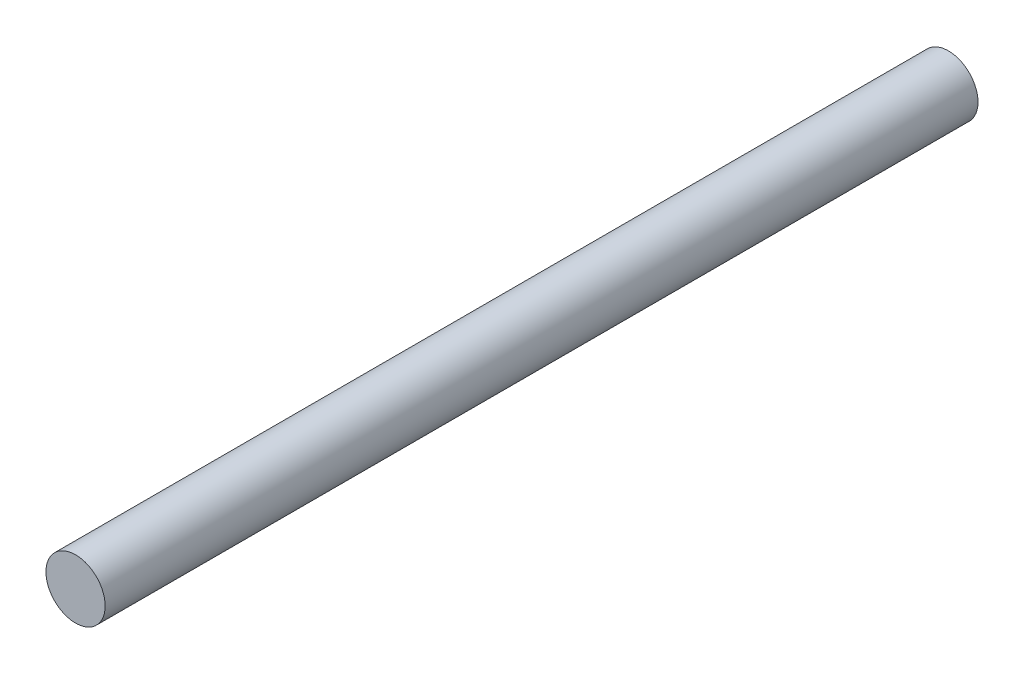
SolidWorks part; units mm, degrees
material "Thornel Mat VMA"
ref_plane "Front Plane" through (0, 0, 0) normal (0, 0, 1) x (1, 0, 0)
ref_plane "Top Plane" through (0, 0, 0) normal (0, 1, 0) x (1, 0, 0)
ref_plane "Right Plane" through (0, 0, 0) normal (1, 0, 0) x (0, 0, -1)
sketch "Sketch1" plane through (0, 0, 0) normal (0, 0, 1) x (1, 0, 0)
  circle A0 centre (0, 0) radius 9
  dimension "D1" = 18
extrude "Boss-Extrude1" add sketch "Sketch1" along normal blind 265.32
equation "\"fuse_diam\"= 0.07"
equation "\"fuse_rad\"= 0.035"
equation "\"battery_length\"= 0.076"
equation "\"battery_width\"= 0.034"
equation "\"battery_height\"= 0.051"
equation "\"bat_bay_length\"= 0.096"
equation "\"wing_shelf\"= 0.0175"
equation "\"shell\"= 0.002"
equation "\"chord_length\"= 0.089"
equation "\"tail_length\"= 0.26532000000000006"
equation "\"tail_diam\"= 0.035"
equation "\"connector\"= 0.06633000000000001"
equation "\"D1@Boss-Extrude1\"=\"tail_length\""
